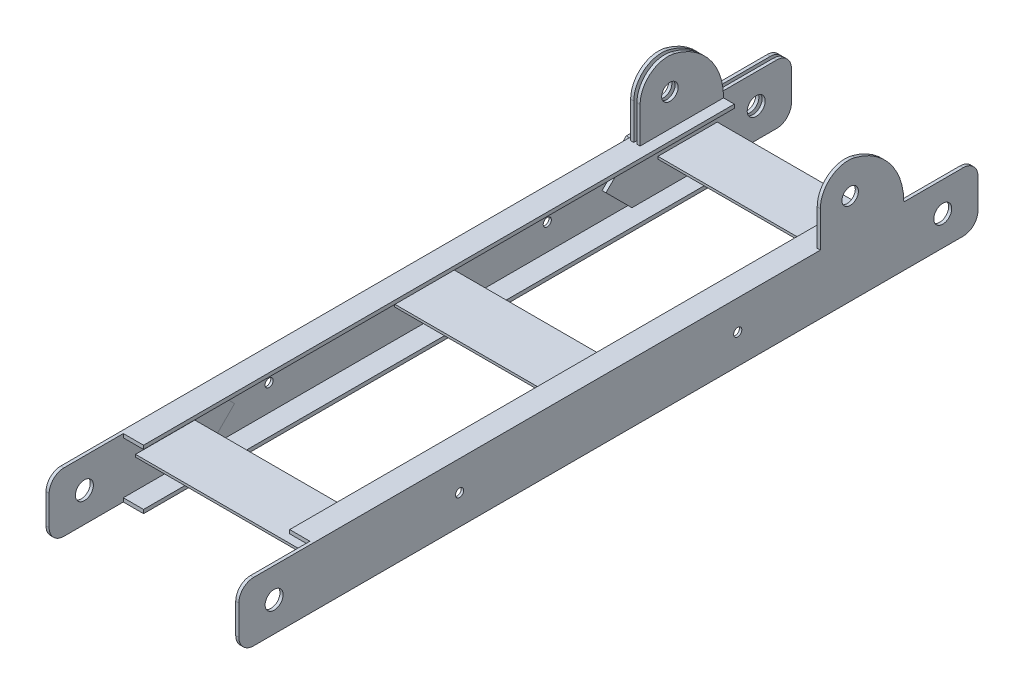
SolidWorks part; units mm, degrees
ref_plane "前视基准面" through (0, 0, 0) normal (0, 0, 1) x (1, 0, 0)
ref_plane "上视基准面" through (0, 0, 0) normal (0, 1, 0) x (1, 0, 0)
ref_plane "右视基准面" through (0, 0, 0) normal (1, 0, 0) x (0, 0, -1)
sketch "草图2" plane through (0, 0, 0) normal (0, 0, 1) x (1, 0, 0)
  line L0 (0, 0) -> (0, 160)
  line L1 (0, 160) -> (63, 160)
  line L2 (63, 160) -> (63, 150)
  line L3 (63, 150) -> (6.5, 150)
  line L4 (6.5, 150) -> (6.5, 10)
  line L5 (6.5, 10) -> (63, 10)
  line L6 (63, 10) -> (63, 0)
  line L7 (63, 0) -> (0, 0)
  line L8 (457, 160) -> (520, 160)
  line L9 (520, 160) -> (520, 0)
  line L10 (520, 0) -> (457, 0)
  line L11 (457, 0) -> (457, 10)
  line L12 (457, 10) -> (513.5, 10)
  line L13 (513.5, 10) -> (513.5, 150)
  line L14 (513.5, 150) -> (457, 150)
  line L15 (457, 150) -> (457, 160)
  dimension "D1" = 160
  dimension "D2" = 10
  dimension "D3" = 6.5
  dimension "D4" = 63
  dimension "D5" = 520
extrude "拉伸1" add sketch "草图2" along normal blind 1992.7756
sketch "草图5" plane through (0, 0, 0) normal (-1, 0, 0) x (0, 0, 1)
  line L0 (200, 95) -> (360, 95)
  line L1 (360, 95) -> (360, 88.5)
  line L2 (283.25, 88.5) -> (360, 88.5)
  line L3 (283.25, 88.5) -> (283.25, 48.5)
  line L4 (283.25, 48.5) -> (276.75, 48.5)
  line L5 (276.75, 48.5) -> (276.75, 88.5)
  line L6 (276.75, 88.5) -> (200, 88.5)
  line L7 (200, 88.5) -> (200, 95)
  line L8 (0, 160) -> (0, 0) construction
  point P10 (0, 80)
  dimension "D1" = 160
  dimension "D2" = 6.5
  dimension "D3" = 6.5
  dimension "D4" = 40
  dimension "D5" = 200
  dimension "D6" = 15
extrude "拉伸3" add sketch "草图5" against normal blind 520
pattern_linear "阵列(线性)1" count 3 spacing 700 along (0, 0, 1) of "拉伸3"
sketch "草图7" plane through (513.5, 0, 0) normal (-1, 0, 0) x (0, 0, 1)
  line L0 (1992.7756, 10) -> (0, 10) construction
  line L1 (0, 10) -> (500, 10)
  line L2 (0, 10) -> (0, 150)
  line L3 (0, 150) -> (500, 150)
  line L4 (1562.7756, 150) -> (1492.7756, 80)
  line L5 (1992.7756, 150) -> (0, 150) construction
  line L6 (1992.7756, 150) -> (1992.7756, 10) construction
  line L7 (1992.7756, 10) -> (1562.7756, 10)
  line L8 (1992.7756, 10) -> (1992.7756, 150)
  line L9 (1992.7756, 150) -> (1562.7756, 150)
  line L10 (1492.7756, 80) -> (1562.7756, 10)
  line L11 (0, 150) -> (0, 10) construction
  line L12 (500, 150) -> (570, 80)
  line L13 (570, 80) -> (500, 10)
  dimension "D1" = 500
  dimension "D2" = 500
extrude "拉伸5" add sketch "草图7" along normal blind 2
sketch "草图15" plane through (6.5, 0, 0) normal (1, 0, 0) x (0, 0, -1)
  line L0 (-1992.7756, 10) -> (0, 10) construction
  line L1 (-1992.7756, 150) -> (-1562.7756, 150)
  line L2 (-1992.7756, 150) -> (-1992.7756, 10)
  line L3 (-1992.7756, 10) -> (-1562.7756, 10)
  line L4 (-1562.7756, 150) -> (-1492.7756, 80)
  line L5 (-1992.7756, 150) -> (0, 150) construction
  line L6 (0, 10) -> (0, 150) construction
  line L7 (-430, 150) -> (0, 150)
  line L8 (-1492.7756, 80) -> (-1562.7756, 10)
  line L9 (-430, 10) -> (0, 10)
  line L10 (0, 150) -> (0, 10)
  line L11 (-430, 150) -> (-500, 80)
  line L12 (-500, 80) -> (-430, 10)
  dimension "D1" = 500
extrude "拉伸8" add sketch "草图15" along normal blind 2
sketch "草图19" plane through (0, 0, 0) normal (-1, 0, 0) x (0, 0, 1)
  line L0 (1992.7756, 0) -> (0, 0) construction
  line L1 (0, 160) -> (420, 160)
  line L2 (0, 160) -> (0, 0)
  line L3 (0, 0) -> (420, 0)
  line L4 (420, 160) -> (500, 80)
  line L5 (500, 80) -> (420, 0)
  dimension "D1" = 500
extrude "拉伸11" add sketch "草图19" along normal blind 8.5
pattern_linear "阵列(线性)2" count 2 spacing 17 along (1, 0, 0) of "拉伸11"
sketch "草图6" plane through (0, 160, 0) normal (0, 1, 0) x (1, 0, 0)
  line L0 (520, 0) -> (457, 0) construction
  line L1 (511.5, 0) -> (17, 0)
  line L2 (511.5, 0) -> (511.5, -200)
  line L3 (511.5, -200) -> (17, -200)
  line L4 (17, 0) -> (17, -200)
  line L5 (63, -1992.7756) -> (0, -1992.7756) construction
  line L6 (511.5, -1792.7756) -> (8.5, -1792.7756)
  line L7 (511.5, -1792.7756) -> (511.5, -1992.7756)
  line L8 (511.5, -1992.7756) -> (8.5, -1992.7756)
  line L9 (8.5, -1792.7756) -> (8.5, -1992.7756)
  line L10 (520, -1992.7756) -> (520, 0) construction
  line L11 (0, -1992.7756) -> (0, -420) construction
  line L12 (63, 0) -> (-8.5, 0) construction
  line L13 (0, 0) -> (8.5, 0)
  line L14 (0, 0) -> (0, -200)
  line L15 (0, -200) -> (8.5, -200)
  line L16 (8.5, 0) -> (8.5, -200)
  dimension "D1" = 8.5
  dimension "D2" = 8.5
  dimension "D3" = 200
  dimension "D4" = 200
  dimension "D5" = 8.5
  dimension "D6" = 17
  dimension "D7" = 8.5
  dimension "D8" = 8.5
extrude "拉伸12" cut sketch "草图6" against normal through all
sketch "草图20" plane through (-8.5, 0, 0) normal (-1, 0, 0) x (0, 0, 1)
  line L0 (0, 80) -> (1992.7756, 80) construction
  line L1 (0, 160) -> (0, 0) construction
  line L2 (1992.7756, 160) -> (1992.7756, 0) construction
  circle A0 centre (95, 80) radius 24.25
  circle A1 centre (1897.7756, 80) radius 24.25
  dimension "D1" = 48.5
  dimension "D2" = 95
  dimension "D3" = 95
extrude "拉伸13" cut sketch "草图20" against normal through all
fillet "圆角1" radius 40 10 edges at (4.25, 0, 1992.7756) (4.25, 160, 1992.7756) (515.75, 0, 1992.7756) (515.75, 160, 1992.7756) (-4.25, 0, 0) (12.75, 0, 0) (-4.25, 160, 0) (12.75, 160, 0) (515.75, 0, 0) (515.75, 160, 0)
sketch "草图21" plane through (0, 160, 0) normal (0, 1, 0) x (1, 0, 0)
  line L0 (8.5, -200) -> (8.5, -40) construction
  line L1 (520, -200) -> (511.5, -200)
  line L2 (520, -200) -> (520, -425)
  line L3 (520, -425) -> (511.5, -425)
  line L4 (511.5, -200) -> (511.5, -425)
  line L5 (17, -200) -> (8.5, -200)
  line L6 (17, -200) -> (17, -425)
  line L7 (17, -425) -> (8.5, -425)
  line L8 (8.5, -200) -> (8.5, -425)
  line L9 (34, -425) -> (25.5, -425)
  line L10 (34, -425) -> (34, -200)
  line L11 (34, -200) -> (25.5, -200)
  line L12 (25.5, -425) -> (25.5, -200)
  line L13 (520, -1952.7756) -> (520, -40) construction
  line L14 (0, -200) -> (8.5, -200) construction
  dimension "D1" = 225
  dimension "D2" = 8.5
  dimension "D3" = 8.5
extrude "拉伸14" add sketch "草图21" along normal blind 175
sketch "草图22" plane through (-8.5, 0, 0) normal (-1, 0, 0) x (0, 0, 1)
  line L0 (95, 80) -> (1897.7756, 80) construction
  line L1 (95, 80) -> (344.6151, 246.4101) construction
  line L2 (344.6151, 246.4101) -> (455.5551, 80) construction
  circle A0 centre (344.6151, 246.4101) radius 22.25
  dimension "D3" = 44.5
  dimension "D1" = 300
  dimension "D2" = 200
extrude "拉伸15" cut sketch "草图22" against normal through all
fillet "圆角2" radius 175 3 edges at (12.75, 335, 200) (515.75, 335, 200) (29.75, 335, 200)
fillet "圆角3" radius 75 3 edges at (12.75, 335, 425) (515.75, 335, 425) (29.75, 335, 425)
sketch "草图23" plane through (520, 0, 0) normal (1, 0, 0) x (0, 0, -1)
  line L0 (-1897.7756, 80) -> (-95, 80) construction
  circle A0 centre (-1397.7756, 80) radius 11
  circle A1 centre (-647.7756, 80) radius 11
  dimension "D1" = 22
  dimension "D2" = 500
  dimension "D3" = 750
extrude "拉伸16" cut sketch "草图23" against normal through all
